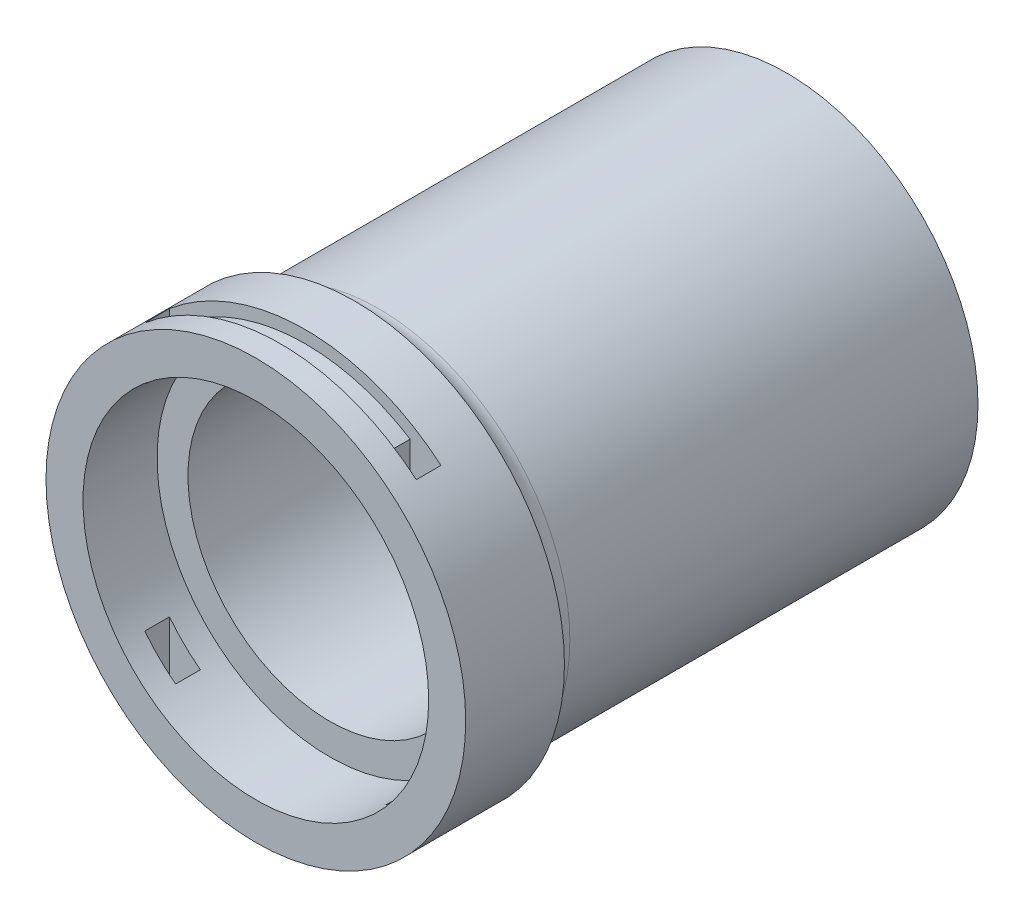
SolidWorks part; units mm, degrees
material "ABS"
ref_plane "Front Plane" through (0, 0, 0) normal (0, 0, 1) x (1, 0, 0)
ref_plane "Top Plane" through (0, 0, 0) normal (0, 1, 0) x (1, 0, 0)
ref_plane "Right Plane" through (0, 0, 0) normal (1, 0, 0) x (0, 0, -1)
sketch "Sketch1" plane through (0, 0, 0) normal (0, 0, 1) x (1, 0, 0)
  circle A0 centre (0, 0) radius 15.5
  dimension "D1" = 31
extrude "Boss-Extrude5" add sketch "Sketch1" along normal blind 26 and the other way blind 17 contours A0
sketch "Sketch3" plane through (0, 0, 26) normal (0, 0, 1) x (1, 0, 0)
  circle A0 centre (0, 0) radius 5.625
  dimension "D1" = 11.25
extrude "Cut-Extrude2" cut sketch "Sketch3" against normal through all
sketch "Sketch4" plane through (0, 0, 26) normal (0, 0, 1) x (1, 0, 0)
  circle A0 centre (0, 0) radius 11.5
  circle A2 centre (0, 0) radius 15.5 construction
  dimension "D1" = 23
  dimension "D2" = 4
extrude "Cut-Extrude3" cut sketch "Sketch4" against normal blind 20 and the other way blind 28
sketch "Sketch7" plane through (0, 0, 0) normal (0, 0, 1) x (1, 0, 0)
  circle A1 centre (0, 0) radius 11.5
  circle A2 centre (0, 0) radius 8.5
  dimension "D1" = 17
  dimension "D2" = 23
extrude "Cut-Extrude6" cut sketch "Sketch7" against normal blind 18 from surface starting at face at (11.5, 0, 6)
sketch "Sketch12" plane through (0, 0, 0) normal (0, 0, 1) x (1, 0, 0)
  circle A0 centre (0, 0) radius 17
  dimension "D1" = 34
extrude "Boss-Extrude8" add sketch "Sketch12" along normal up to surface (26 mm away) and the other way blind 2 from offset 20 up to face at (15.5, 0, 26)
sketch "Sketch13" plane through (0, 0, 0) normal (0, 0, 1) x (1, 0, 0)
  circle A0 centre (0, 0) radius 11.5
  dimension "D1" = 23
extrude "Cut-Extrude10" cut sketch "Sketch13" along normal through all from surface starting at face at (11.5, 0, 18)
fillet "Fillet2" radius 2 1 edges at (15.5, 0, 18)
sketch "Sketch14" plane through (0, 0, 0) normal (0, 0, 1) x (1, 0, 0)
  circle A0 centre (0, 0) radius 14
  dimension "D1" = 28
extrude "Cut-Extrude11" cut sketch "Sketch14" against normal blind 6 from surface starting at face at (17, 0, 26)
sketch "Sketch15" plane through (0, 0, 0) normal (0, 0, 1) x (1, 0, 0)
  circle A0 centre (0, 10) radius 0.5
  circle A1 centre (0, 0) radius 11.5 construction
  circle A3 centre (0, -10) radius 0.5
  circle A4 centre (10, 0) radius 0.5
  circle A5 centre (-10, 0) radius 0.5
  dimension "D1" = 10
extrude "Cut-Extrude14" cut sketch "Sketch15" along normal through all and the other way through all contours A3 | A4 | A0 | A5
sketch "Sketch18" plane through (0, 0, 0) normal (0, 1, 0) x (1, 0, 0)
  line L0 (-17, -26) -> (17, -26) construction
  line L1 (11, -22) -> (-11, -22) construction
  line L2 (11, -22) -> (11, -24)
  line L3 (11, -24) -> (-11, -24) construction
  line L4 (-11, -22) -> (-11, -24)
  line L5 (11, -22) -> (-11, -24) construction
  line L6 (11, -24) -> (-11, -22) construction
  line L7 (-11, -24) -> (-8.5, -24)
  line L8 (-11, -24) -> (-11, -22)
  line L9 (-11, -22) -> (-8.5, -22)
  line L10 (-8.5, -24) -> (-8.5, -22)
  line L11 (11, -24) -> (8.5, -24)
  line L12 (11, -24) -> (11, -22)
  line L13 (11, -22) -> (8.5, -22)
  line L14 (8.5, -24) -> (8.5, -22)
  line L15 (-11, -22) -> (-8.5, -22)
  line L16 (-11, -24) -> (-8.5, -24)
  line L17 (8.5, -22) -> (11, -22)
  line L18 (8.5, -24) -> (11, -24)
  point P0 (0, -23)
  dimension "D1" = 2
  dimension "D2" = 2.5
  dimension "D3" = 2.5
  dimension "D4" = 17
  dimension "D5" = 0
  dimension "D6" = 2
extrude "Cut-Extrude15" cut sketch "Sketch18" against normal mid plane 40 contours L7 L10 L9 L4 | L14 L11 L2 L13 region at (9.75, 0, 23) region at (-9.75, 0, 23)
ref_plane "Plane1" through (0, 0, 24) normal (0, 0, -1) x (-1, 0, 0)
sketch "Sketch23" plane through (0, 0, 24) normal (0, 0, -1) x (-1, 0, 0)
  line L0 (9.7192, 13.9477) -> (9.1475, 13.1272)
  line L1 (-9.1475, 13.1272) -> (-9.7192, 13.9477)
  line L2 (-9.1475, -13.1272) -> (-9.7192, -13.9477)
  line L3 (9.7192, -13.9477) -> (9.1475, -13.1272)
  arc A0 (9.1475, 13.1272) -> (-9.1475, 13.1272) centre (0, 0) ccw
  arc A1 (9.1475, -13.1272) -> (-9.1475, -13.1272) centre (0, 0) cw
  arc A2 (9.7192, 13.9477) -> (-9.7192, 13.9477) centre (0, 0) ccw
  arc A3 (-9.7192, -13.9477) -> (9.7192, -13.9477) centre (0, 0) ccw
  dimension "D1" = 1
  dimension "D2" = 17
extrude "Cut-Extrude16" cut sketch "Sketch23" along normal blind 2
sketch "Sketch26" plane through (0, 0, -17) normal (0, 0, -1) x (-1, 0, 0)
  circle A0 centre (0, 0) radius 15.5
  circle A1 centre (0, 0) radius 5.625
  circle A2 centre (-10, 0) radius 0.5
  circle A3 centre (0, 10) radius 0.5
  circle A4 centre (10, 0) radius 0.5
  circle A5 centre (0, -10) radius 0.5
  point P16 (0, 0)
  dimension "D1" = 1
  dimension "D2" = 11.25
  dimension "D3" = 31
  dimension "D5" = 10
  dimension "D6" = 10
  dimension "D4" = 4
ref_plane "Plane2" through (0, 0, -17) normal (0, 0, -1) x (-1, 0, 0)
sketch "Sketch28" plane through (0, 0, -17) normal (0, 0, -1) x (-1, 0, 0)
  circle A0 centre (0, 0) radius 6.875
  dimension "D1" = 13.75
extrude "Cut-Extrude17" cut sketch "Sketch28" against normal blind 16
